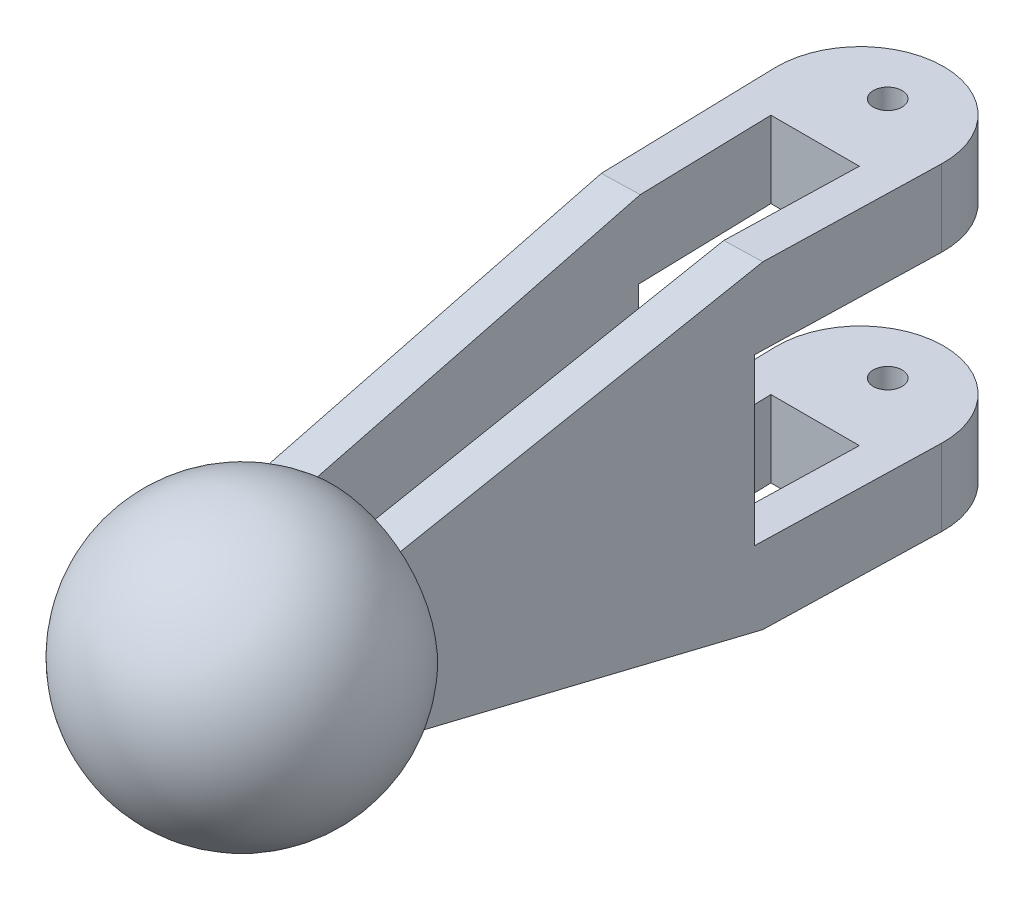
SolidWorks part; units mm, degrees
ref_plane "Front Plane" through (0, 0, 0) normal (0, 0, 1) x (1, 0, 0)
ref_plane "Top Plane" through (0, 0, 0) normal (0, 1, 0) x (1, 0, 0)
ref_plane "Right Plane" through (0, 0, 0) normal (1, 0, 0) x (0, 0, -1)
sketch "Sketch1" plane through (0, 0, 0) normal (0, 1, 0) x (1, 0, 0)
  line L0 (-13.9448, -0.3652) -> (-11.6169, -89.2652)
  line L1 (13.9448, -0.3652) -> (11.6169, -89.2652)
  line L2 (0, 15.9405) -> (0, -57.1464) construction
  arc A0 (13.9448, -0.3652) -> (-13.9448, -0.3652) centre (0, 0) ccw
  arc A1 (-11.6169, -89.2652) -> (11.6169, -89.2652) centre (0, -95.9895) ccw
  dimension "D2" = 1.5
  dimension "D3" = 1.5
  dimension "D4" = 88.9
  dimension "D5" = 88.9
extrude "Boss-Extrude1" add sketch "Sketch1" along normal blind 53.34 contours L0 A1 L1 A0
ref_plane "Plane1" through (0, 0, 0.3652) normal (0, 0, -1) x (-1, 0, 0)
sketch "Sketch2" plane through (0, 0, 0.3652) normal (0, 0, -1) x (-1, 0, 0)
  line L1 (-13.8535, 41.783) -> (16.0684, 41.783)
  line L2 (-13.8535, 41.783) -> (-13.8535, 37.211)
  line L3 (-13.8535, 37.211) -> (16.0684, 37.211)
  line L4 (16.0684, 41.783) -> (16.0684, 37.211)
  line L5 (13.4226, 53.34) -> (-13.4226, 53.34) construction
  dimension "D1" = 4.572
  dimension "D2" = 11.557
sketch "Sketch3" plane through (0, 0, 0) normal (0, -1, 0) x (1, 0, 0)
  line L0 (-5.2137, 91.2104) -> (-7.404, 7.5684)
  line L1 (7.404, 7.5684) -> (5.2137, 91.2104)
  line L2 (13.9448, 0.3652) -> (11.6169, 89.2652)
  line L3 (-11.6169, 89.2652) -> (-13.9448, 0.3652)
  line L4 (13.9448, 0.3652) -> (11.6169, 89.2652)
  line L5 (-11.6169, 89.2652) -> (-13.9448, 0.3652)
  line L6 (7.404, 7.5684) -> (-11.1568, 7.5684)
  line L7 (7.597, 0.1989) -> (5.2137, 91.2104) construction
  line L8 (-5.2137, 91.2104) -> (-7.597, 0.1989) construction
  arc A2 (-13.9448, 0.3652) -> (13.9448, 0.3652) centre (0, 0) ccw
  arc A3 (11.6169, 89.2652) -> (-11.6169, 89.2652) centre (0, 95.9895) ccw
  arc A4 (-13.9448, 0.3652) -> (13.9448, 0.3652) centre (0, 0) ccw
  arc A5 (11.6169, 89.2652) -> (-11.6169, 89.2652) centre (0, 95.9895) ccw
  arc A7 (5.2137, 91.2104) -> (-5.2137, 91.2104) centre (0, 95.9895) ccw construction
  arc A8 (5.2137, 91.2104) -> (-5.2137, 91.2104) centre (0, 97.3127) ccw
  arc A10 (-7.597, 0.1989) -> (7.597, 0.1989) centre (0, 0) ccw construction
  dimension "D1" = 0
  dimension "D2" = 6.35
sketch "Sketch4" plane through (13.9448, 0, 0.3652) normal (0.9997, 0, 0.0262) x (0.0262, 0, -0.9997)
  line L0 (0, 53.34) -> (0, 0) construction
  line L1 (-30.5363, 12.827) -> (30.5363, 12.827)
  line L2 (-30.5363, 12.827) -> (-30.5363, 40.513)
  line L3 (-30.5363, 40.513) -> (30.5363, 40.513)
  line L4 (30.5363, 12.827) -> (30.5363, 40.513)
  line L5 (-30.5363, 12.827) -> (30.5363, 40.513) construction
  line L6 (-30.5363, 40.513) -> (30.5363, 12.827) construction
  point P0 (0, 26.67)
  dimension "D1" = 27.686
extrude "Cut-Extrude3" cut sketch "Sketch4" against normal through all
sketch "Sketch5" plane through (0, 53.34, 0) normal (0, 1, 0) x (1, 0, 0)
  line L0 (7.404, -7.5684) -> (5.2137, -91.2104) construction
  line L1 (-5.2137, -91.2104) -> (-7.404, -7.5684) construction
  line L2 (-13.9448, -0.3652) -> (-11.6169, -89.2652)
  line L3 (11.6169, -89.2652) -> (13.9448, -0.3652)
  line L4 (-13.9448, -0.3652) -> (-11.6169, -89.2652)
  line L5 (11.6169, -89.2652) -> (13.9448, -0.3652)
  line L6 (7.404, -7.5684) -> (-11.1568, -7.5684) construction
  line L7 (7.404, -7.5684) -> (5.2137, -91.2104)
  line L8 (-5.2137, -91.2104) -> (-7.404, -7.5684)
  line L9 (7.404, -7.5684) -> (-7.404, -7.5684)
  arc A0 (-5.2137, -91.2104) -> (5.2137, -91.2104) centre (0, -97.3127) ccw construction
  arc A1 (-5.2137, -91.2104) -> (5.2137, -91.2104) centre (0, -97.3127) ccw
  arc A2 (13.9448, -0.3652) -> (-13.9448, -0.3652) centre (0, 0) ccw
  arc A3 (-11.6169, -89.2652) -> (11.6169, -89.2652) centre (0, -95.9895) ccw
  arc A4 (13.9448, -0.3652) -> (-13.9448, -0.3652) centre (0, 0) ccw
  arc A5 (-11.6169, -89.2652) -> (11.6169, -89.2652) centre (0, -95.9895) ccw
  dimension "D1" = 0
extrude "Cut-Extrude5" cut sketch "Sketch5" against normal through all flip side to cut
sketch "Sketch6" plane through (0, 53.34, 0) normal (0, 1, 0) x (1, 0, 0)
  circle A0 centre (0, 4.5787) radius 2.413
  dimension "D1" = 4.826
extrude "Cut-Extrude6" cut sketch "Sketch6" against normal through all
sketch "Sketch7" plane through (-13.9448, 0, 0.3652) normal (-0.9997, 0, 0.0262) x (0.0262, 0, 0.9997)
  line L0 (88.9305, 26.67) -> (-49.4986, 26.67) construction
  line L2 (88.9305, 26.67) -> (88.9305, 40.09)
  line L3 (88.9305, 53.34) -> (88.9305, 0) construction
  line L4 (88.9305, 26.67) -> (88.9305, 13.25)
  line L5 (29.8472, 12.827) -> (29.8472, 0)
  line L6 (0, 0) -> (88.9305, 0) construction
  line L7 (29.8472, 40.513) -> (29.8472, 53.34)
  line L8 (0, 53.34) -> (88.9305, 53.34) construction
  line L9 (29.8472, 0) -> (88.9305, 13.25)
  line L10 (29.8472, 53.34) -> (88.9305, 40.09)
  line L11 (29.8472, 53.34) -> (138.7027, 53.34)
  line L12 (138.7027, 53.34) -> (138.7027, 0)
  line L13 (138.7027, 0) -> (29.8472, 0)
  line L14 (88.9305, 13.25) -> (115.1967, 13.25)
  line L15 (115.1967, 13.25) -> (115.1967, 40.09)
  line L16 (115.1967, 40.09) -> (88.9305, 40.09)
  line M7 (0, 0) -> (88.9305, 0)
  line M8 (88.9305, 0) -> (88.9305, 53.34)
  line M9 (88.9305, 53.34) -> (0, 53.34)
  dimension "D1" = 13.42
  dimension "D2" = 13.42
extrude "Cut-Extrude8" cut sketch "Sketch7" against normal blind 100 and the other way blind 100 contours L12 L0 L15 L14 L13 M8 | L0 L12 L11 L16 L15 M8 | L10 M9 M8 | L9 M7 M8 region at (-10.8542, 26.67, 118.3907) region at (-12.1324, 48.9233, 69.5775) region at (-12.1324, 4.4167, 69.5775)
sketch "Sketch8" plane through (0, 40.09, 0) normal (0, 1, 0) x (1, 0, 0)
  line L0 (-11.6169, -89.2652) -> (19.7485, -88.4438)
  line L1 (19.7485, -88.4438) -> (21.1363, -119.7324)
  line L2 (21.1363, -119.7324) -> (-27.7693, -116.2194)
  line L3 (-27.7693, -116.2194) -> (-20.4659, -89.2652)
  line L4 (-20.4659, -89.2652) -> (-11.6169, -89.2652)
extrude "Cut-Extrude9" cut sketch "Sketch8" against normal blind 100
ref_plane "Plane2" through (0, 0, 0) normal (-1, 0, 0) x (0, 0, 1)
sketch "Sketch12" plane through (2.3279, 0, 88.9) normal (0.0262, 0, 0.9997) x (0.9997, 0, -0.0262)
  line L0 (-13.9496, 40.09) -> (-7.5996, 13.4527)
  line L1 (-7.5996, 40.09) -> (-7.5996, 13.25) construction
  line L2 (-13.9496, 13.25) -> (-7.5996, 40.09)
  line L5 (-10.7746, 26.7713) -> (-13.9496, 26.7713)
  line L6 (-13.9496, 40.09) -> (-13.9496, 13.25) construction
ref_plane "Plane4" through (0, 26.7713, 0) normal (0, 1, 0) x (-0.9997, 0, 0.0262)
sketch "Sketch18" plane through (2.3279, 0, 88.9) normal (0.0262, 0, 0.9997) x (0.9997, 0, -0.0262)
  line L0 (9.3081, 13.25) -> (9.3081, 40.09) construction
  line L1 (9.3081, 26.67) -> (-13.9496, 26.7713)
  circle A0 centre (-2.3208, 26.7207) radius 17.7191
sketch "Sketch14" plane through (0, 26.7713, 0) normal (0, 1, 0) x (-0.9997, 0, 0.0262)
  line L1 (13.9496, 88.9305) -> (-9.3081, 88.9305)
  line L2 (2.3208, 88.9305) -> (2.3208, 103.9214)
  line L3 (20.0399, 88.9305) -> (-15.3984, 88.9305) construction
  line L4 (20.0399, 88.9305) -> (-15.3984, 88.9305)
  line L5 (2.3208, 103.9214) -> (2.3208, 127.1312)
  circle A0 centre (2.3208, 103.9214) radius 23.2098
revolve "Revolve6" add sketch "Sketch14" angle 360 about L5 region at (-9.7908, 26.7713, 106.7033)
